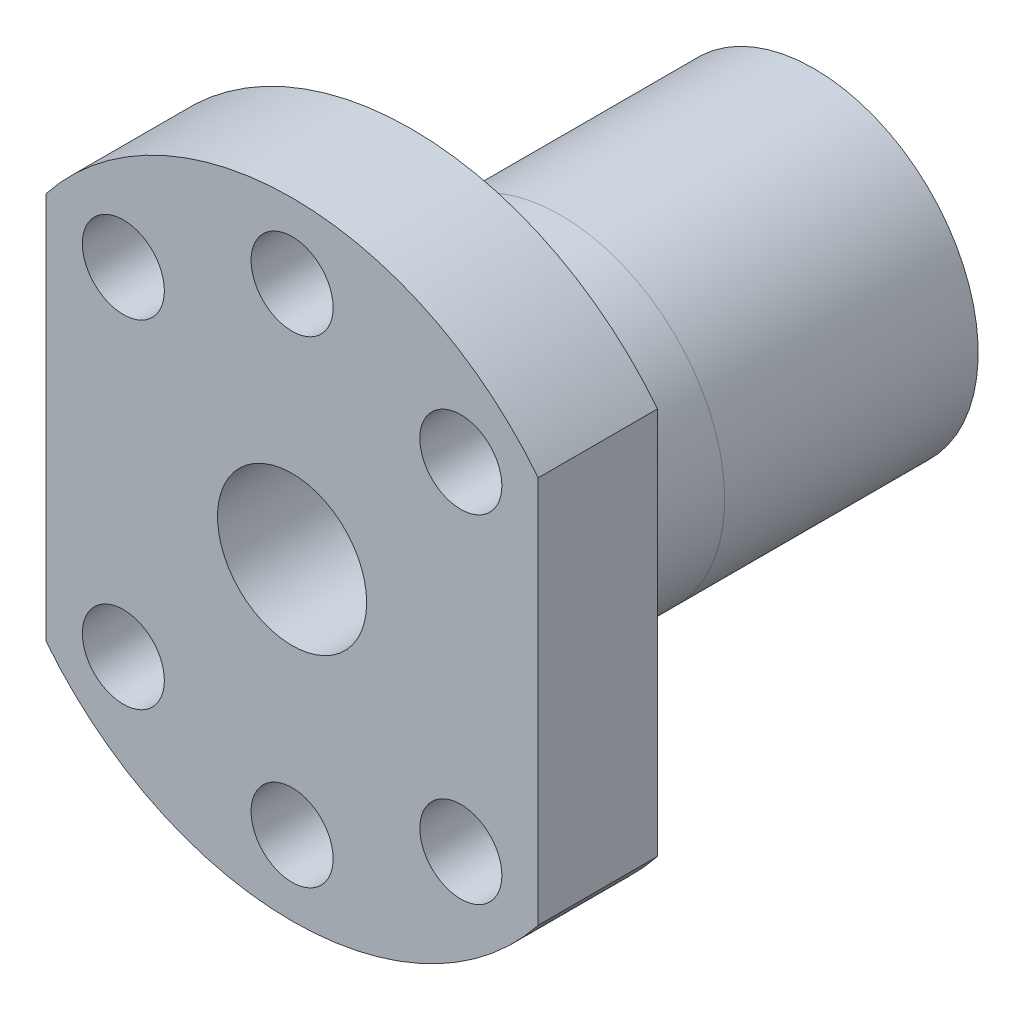
SolidWorks part; units mm, degrees
ref_plane "前视基准面" through (0, 0, 0) normal (0, 0, 1) x (1, 0, 0)
ref_plane "上视基准面" through (0, 0, 0) normal (0, 1, 0) x (1, 0, 0)
ref_plane "右视基准面" through (0, 0, 0) normal (1, 0, 0) x (0, 0, -1)
sketch "草图1" plane through (0, 0, 0) normal (0, 0, 1) x (1, 0, 0)
  line L0 (0, 0) -> (16, 0) construction
  line L1 (0, 0) -> (0, -16) construction
  line L2 (0, 0) -> (11.3137, 11.3137) construction
  line L3 (0, 0) -> (-11.3137, 11.3137) construction
  line L4 (0, 0) -> (6.1229, -14.7821) construction
  line L5 (-8, 13.8564) -> (0, 0) construction
  line L6 (0, 0) -> (8, 13.8564) construction
  line L7 (-16.5, -12.9904) -> (-16.5, 12.9904)
  line L8 (16.5, 12.9904) -> (16.5, -12.9904)
  line L9 (0, 0) -> (1.8478, 0.7654)
  line L10 (1.8478, 0.7654) -> (9.8841, -18.6361)
  line L11 (9.8841, -18.6361) -> (8.0364, -19.4015)
  line L12 (1.4782, 0.6123) -> (7.2185, -13.2459)
  line L13 (7.2185, -13.2459) -> (7.588, -13.0928)
  line L14 (-12, -17.2337) -> (-12, 17.2337)
  line L15 (12, 17.2337) -> (12, -17.2337)
  circle A0 centre (0, 0) radius 21
  circle A1 centre (0, 0) radius 16 construction
  circle A2 centre (11.3137, 11.3137) radius 2.75
  circle A3 centre (-11.3137, 11.3137) radius 2.75
  circle A4 centre (0, 16) radius 2.75
  circle A5 centre (-8, 13.8564) radius 2.75
  circle A6 centre (8, 13.8564) radius 2.75
  circle A7 centre (0, 0) radius 5
  point P21 (0, 21)
  dimension "D1" = 90
  dimension "D6" = 42
  dimension "(D4)" = 32
  dimension "D5" = 5.5
  dimension "D2" = 3.2
  dimension "(d)" = 10
  dimension "JD" = 22.5
  dimension "D3" = 60
  dimension "D4" = 6
  dimension "L5" = 33
  dimension "Q" = 4
  dimension "L6" = 24
sketch "草图2" plane through (0, 0, 0) normal (1, 0, 0) x (0, 0, -1)
  line L0 (-4, 0) -> (31, 0) construction
  line L1 (-4, 0) -> (-4, 21)
  line L2 (-4, 21) -> (4, 21)
  line L3 (4, 21) -> (4, 11)
  line L4 (4, 11) -> (31, 11)
  line L5 (31, 11) -> (31, 0)
  line L6 (0, 0) -> (0, 21) construction
  line L7 (14, 11) -> (14, 0)
  line L8 (-75, 0) -> (75, 0) construction
  line L9 (75, 0) -> (-40, 0)
  dimension "D1" = 22
  dimension "L1" = 35
  dimension "L2" = 8
  dimension "L7" = 10
  dimension "ZL" = 150
  dimension "D3" = 115
sketch "草图3" plane through (0, 0, 0) normal (1, 0, 0) x (0, 0, -1)
  line L0 (-4, 0) -> (-4, 21) construction
  line L1 (-4, 21) -> (4, 21) construction
  line L2 (4, 21) -> (4, 11) construction
  line L3 (4, 11) -> (31, 11) construction
  line L4 (31, 11) -> (31, 0) construction
  line L5 (-4, 0) -> (-4, 21)
  line L6 (-4, 21) -> (4, 21)
  line L7 (4, 21) -> (4, 11)
  line L8 (4, 11) -> (31, 11)
  line L9 (31, 11) -> (31, 0)
  line L10 (-4, 0) -> (31, 0)
revolve "旋转1" add sketch "草图3" angle 360 about L10
sketch "草图13" plane through (0, 0, 0) normal (0, 0, 1) x (1, 0, 0)
  line L0 (-16.5, -12.9904) -> (-16.5, 12.9904) construction
  line L1 (16.5, 12.9904) -> (16.5, -12.9904) construction
  line L2 (-16.5, -12.9904) -> (-16.5, 12.9904)
  line L3 (16.5, 12.9904) -> (16.5, -12.9904)
  circle A0 centre (0, 0) radius 21 construction
  arc A1 (-16.5, 12.9904) -> (-16.5, -12.9904) centre (0, 0) ccw
  arc A2 (16.5, -12.9904) -> (16.5, 12.9904) centre (0, 0) ccw
extrude "切除-拉伸7" cut sketch "草图13" along normal up to vertex (4 mm away) from vertex up to point (0, 21, 4) starting at point (0, 21, -4)
sketch "草图5" plane through (0, 0, 0) normal (0, 0, 1) x (1, 0, 0)
  circle A0 centre (-11.3137, 11.3137) radius 2.75 construction
  circle A1 centre (11.3137, 11.3137) radius 2.75 construction
  circle A2 centre (-11.3137, 11.3137) radius 2.75
  circle A3 centre (11.3137, 11.3137) radius 2.75
extrude "切除-拉伸2" cut sketch "草图5" along normal up to vertex (4 mm away) from vertex up to point (0, 21, 4) starting at point (0, 21, -4)
mirror "镜向1" about plane through (0, 0, 0) normal (0, 1, 0) of "切除-拉伸2"
sketch "草图6" plane through (0, 0, 0) normal (0, 0, 1) x (1, 0, 0)
  circle A0 centre (0, 16) radius 2.75 construction
  circle A1 centre (0, 16) radius 2.75
extrude "切除-拉伸3" cut sketch "草图6" along normal up to vertex (4 mm away) from vertex up to point (0, 21, 4) starting at point (0, 21, -4)
mirror "镜向2" about plane through (0, 0, 0) normal (0, 1, 0) of "切除-拉伸3"
sketch "草图7" [suppressed] plane through (0, 0, 0) normal (0, 0, 1) x (1, 0, 0)
  circle A0 centre (-5.75, 9.9593) radius 1.7 construction
  circle A1 centre (5.75, 9.9593) radius 1.7 construction
  circle A2 centre (-5.75, 9.9593) radius 1.7
  circle A3 centre (5.75, 9.9593) radius 1.7
extrude "切除-拉伸4" [suppressed] cut sketch "草图7" along normal up to vertex from vertex
mirror "镜向3" [suppressed] about plane through (0, 0, 0) normal (0, 1, 0)
sketch "草图14" [suppressed] plane through (0, 0, 0) normal (0, 0, 1) x (1, 0, 0)
  line L0 (-10, -11.8427) -> (-10, 11.8427) construction
  line L1 (10, 11.8427) -> (10, -11.8427) construction
  line L2 (-10, -11.8427) -> (-10, 11.8427)
  line L3 (10, 11.8427) -> (10, -11.8427)
  circle A0 centre (0, 0) radius 15.5 construction
  arc A1 (-10, 11.8427) -> (-10, -11.8427) centre (0, 0) ccw
  arc A2 (10, -11.8427) -> (10, 11.8427) centre (0, 0) ccw
extrude "切除-拉伸8" [suppressed] cut sketch "草图14" along normal up to vertex from vertex
sketch "草图8" plane through (0, 0, 0) normal (0, 0, 1) x (1, 0, 0)
  circle A0 centre (0, 0) radius 5 construction
  circle A1 centre (0, 0) radius 5
extrude "切除-拉伸5" cut sketch "草图8" against normal through all and the other way through all
cosmetic thread "装饰螺纹线2" parameters "D2"=10.1
sketch "草图11" plane through (0, 0, 0) normal (1, 0, 0) x (0, 0, -1)
  line L0 (14, 11) -> (14, -11)
  line L1 (4, -11) -> (31, -11) construction
split line "分割线1"
sketch "草图10" plane through (0, 0, 0) normal (0, 0, 1) x (1, 0, 0)
  circle A0 centre (0, 0) radius 5 construction
  circle A1 centre (0, 0) radius 5
extrude "凸台-拉伸1" add sketch "草图10" along normal up to vertex (75 mm away) from vertex separate body up to point (0, 0, 75) starting at point (0, 0, -75)
cosmetic thread "装饰螺纹线3" parameters "D2"=8.5
sketch "草图12" [suppressed] plane through (0, 0, 4) normal (0, 0, 1) x (1, 0, 0)
  circle A0 centre (16, 0) radius 2.75
  circle A1 centre (-11.3137, 11.3137) radius 2.75 construction
extrude "切除-拉伸6" [suppressed] cut sketch "草图12" against normal up to vertex
pattern_circular "阵列(圆周)1" [suppressed] count 6 over 360 of bodies 113
delete or keep bodies "实体-删除1" type delete bodies bodies 111
